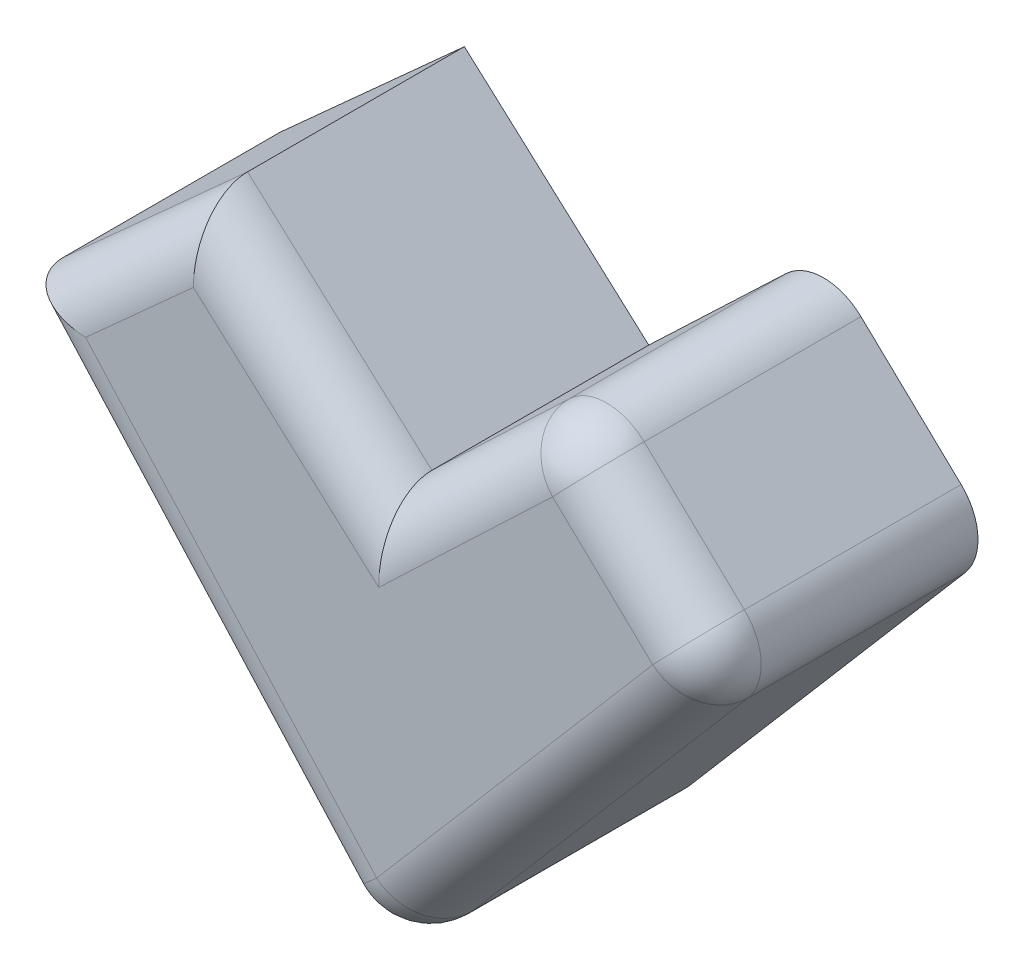
SolidWorks part; units mm, degrees
ref_plane "Front Plane" through (0, 0, 0) normal (0, 0, 1) x (1, 0, 0)
ref_plane "Top Plane" through (0, 0, 0) normal (0, 1, 0) x (1, 0, 0)
ref_plane "Right Plane" through (0, 0, 0) normal (1, 0, 0) x (0, 0, -1)
sketch "Sketch1" plane through (0, 0, 0) normal (0, 0, 1) x (1, 0, 0)
  line L0 (0, 0) -> (-68.0206, 75.4139)
  line L1 (-68.0206, 75.4139) -> (-34.0103, 106.09)
  line L2 (-34.0103, 106.09) -> (0, 75.4139)
  line L3 (0, 75.4139) -> (32.2527, 106.09)
  line L4 (32.2527, 106.09) -> (64.5054, 75.4139)
  line L5 (64.5054, 75.4139) -> (0, 0)
  line L6 (-34.0103, 106.09) -> (-34.0103, -29.4246) construction
  line L7 (32.2527, 106.09) -> (32.2527, -39.0148) construction
  point P8 (0, 0)
  point P9 (0, 0)
  dimension "D1" = 75.4139
  dimension "D2" = 132.526
  dimension "D3" = 106.09
extrude "Boss-Extrude1" add sketch "Sketch1" along normal blind 50
fillet "Fillet1" radius 10 9 edges at (-34.0103, 37.7069, 50) (-51.0155, 90.7519, 50) (-17.0052, 90.7519, 50) (16.1263, 90.7519, 50) (48.379, 90.7519, 50) (32.2527, 37.7069, 50) (0, 0, 25) (64.5054, 75.4139, 25) (32.2527, 106.09, 25)
equation "\"top_height\"=106.09"
equation "\"D3@Sketch1\"=\"top_height\""
equation "\"width\"=132.526"
equation "\"D2@Sketch1\"=\"width\""
equation "\"bottom_height\"=75.4139"
equation "\"D1@Sketch1\"=\"bottom_height\""
equation "\"thick\"=50"
equation "\"D1@Boss-Extrude1\"=\"thick\""
